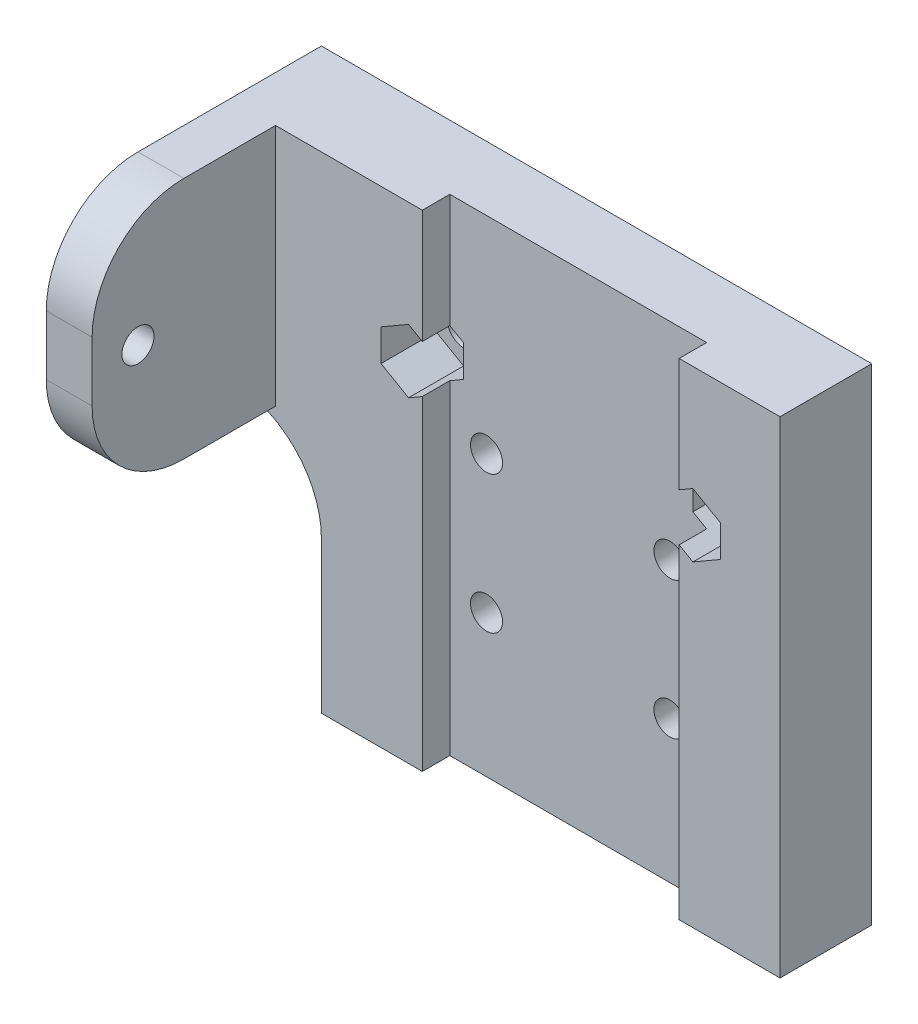
SolidWorks part; units mm, degrees
ref_plane "前视基准面" through (0, 0, 0) normal (0, 0, 1) x (1, 0, 0)
ref_plane "上视基准面" through (0, 0, 0) normal (0, 1, 0) x (1, 0, 0)
ref_plane "右视基准面" through (0, 0, 0) normal (1, 0, 0) x (0, 0, -1)
sketch "草图1" plane through (0, 0, 0) normal (0, 0, 1) x (1, 0, 0)
  line L0 (25, 0) -> (25, -26.5) construction
  line L1 (0, 0) -> (50, 0)
  line L2 (0, 0) -> (0, -53)
  line L3 (0, -53) -> (50, -53)
  line L4 (50, 0) -> (50, -53)
  line L5 (0, -26.5) -> (50, -26.5) construction
  circle A0 centre (35, -22.5) radius 1.75
  circle A1 centre (40.5, -15) radius 1.75
  circle A2 centre (35, -37.5) radius 1.75
  circle A3 centre (15, -37.5) radius 1.75
  circle A4 centre (15, -22.5) radius 1.75
  circle A5 centre (9.5, -15) radius 1.75
  dimension "D3" = 3.5
  dimension "D4" = 20
  dimension "D5" = 15
  dimension "D6" = 7.5
  dimension "D7" = 5.5
  dimension "D8" = 3.5
  dimension "D9" = 3.5
  dimension "D10" = 15.5
  dimension "D11" = 15
  dimension "D1" = 53
  dimension "D2" = 50
extrude "凸台-拉伸1" add sketch "草图1" along normal blind 10
sketch "草图2" plane through (0, 0, 10) normal (0, 0, 1) x (1, 0, 0)
  line L0 (50, 0) -> (0, 0) construction
  line L1 (11, 0) -> (39, 0)
  line L2 (11, 0) -> (11, -53)
  line L3 (11, -53) -> (39, -53)
  line L4 (39, 0) -> (39, -53)
  line L5 (0, -53) -> (50, -53) construction
  line L6 (50, -53) -> (50, 0) construction
  dimension "D1" = 28
  dimension "D2" = 11
extrude "切除-拉伸1" cut sketch "草图2" against normal blind 3
sketch "草图3" plane through (0, 0, 10) normal (0, 0, 1) x (1, 0, 0)
  line L1 (9.5, -18.4641) -> (12.5, -16.7321)
  line L2 (12.5, -16.7321) -> (12.5, -13.2679)
  line L3 (12.5, -13.2679) -> (9.5, -11.5359)
  line L4 (9.5, -11.5359) -> (6.5, -13.2679)
  line L5 (6.5, -13.2679) -> (6.5, -16.7321)
  line L6 (6.5, -16.7321) -> (9.5, -18.4641)
  line L7 (40.5, -18.4641) -> (43.5, -16.7321)
  line L8 (43.5, -16.7321) -> (43.5, -13.2679)
  line L9 (43.5, -13.2679) -> (40.5, -11.5359)
  line L10 (40.5, -11.5359) -> (37.5, -13.2679)
  line L11 (37.5, -13.2679) -> (37.5, -16.7321)
  line L12 (37.5, -16.7321) -> (40.5, -18.4641)
  circle A0 centre (9.5, -15) radius 3 construction
  circle A1 centre (40.5, -15) radius 3 construction
  dimension "D1" = 6
  dimension "D2" = 6
extrude "切除-拉伸2" cut sketch "草图3" against normal blind 6
sketch "草图5" plane through (0, 0, 0) normal (0, 0, -1) x (-1, 0, 0)
  circle A0 centre (-35, -37.5) radius 3
  circle A1 centre (-35, -22.5) radius 3
  circle A2 centre (-15, -37.5) radius 3
  circle A3 centre (-15, -22.5) radius 3
  dimension "D1" = 6
  dimension "D2" = 6
  dimension "D3" = 6
  dimension "D4" = 6
extrude "切除-拉伸4" cut sketch "草图5" against normal blind 3.2
sketch "草图6" plane through (0, 0, 0) normal (0, 0, -1) x (-1, 0, 0)
  line L1 (0, 0) -> (10, 0)
  line L2 (0, 0) -> (0, -26.5)
  line L3 (0, -26.5) -> (10, -26.5)
  line L4 (10, 0) -> (10, -26.5)
  dimension "D1" = 10
  dimension "D2" = 26.5
extrude "凸台-拉伸2" add sketch "草图6" against normal blind 30
sketch "草图7" plane through (0, 0, 30) normal (0, 0, 1) x (1, 0, 0)
  line L0 (-10, 0) -> (0, 0) construction
  line L1 (0, -26.5) -> (-5, -26.5)
  line L2 (0, -26.5) -> (0, 0)
  line L3 (0, 0) -> (-5, 0)
  line L4 (-5, -26.5) -> (-5, 0)
extrude "切除-拉伸5" cut sketch "草图7" against normal blind 20
fillet "圆角2" radius 10 2 edges at (-7.5, 0, 30) (-7.5, -26.5, 30)
fillet "圆角3" radius 10 1 edges at (0, -26.5, 5)
sketch "草图8" plane through (-5, 0, 0) normal (1, 0, 0) x (0, 0, -1)
  line L0 (-10, 0) -> (-10, -26.5) construction
  line L1 (-10, 0) -> (-20, 0) construction
  circle A0 centre (-25, -13.25) radius 1.75
  dimension "D1" = 3.5
  dimension "D2" = 15
  dimension "D3" = 13.25
extrude "切除-拉伸6" cut sketch "草图8" against normal blind 20
